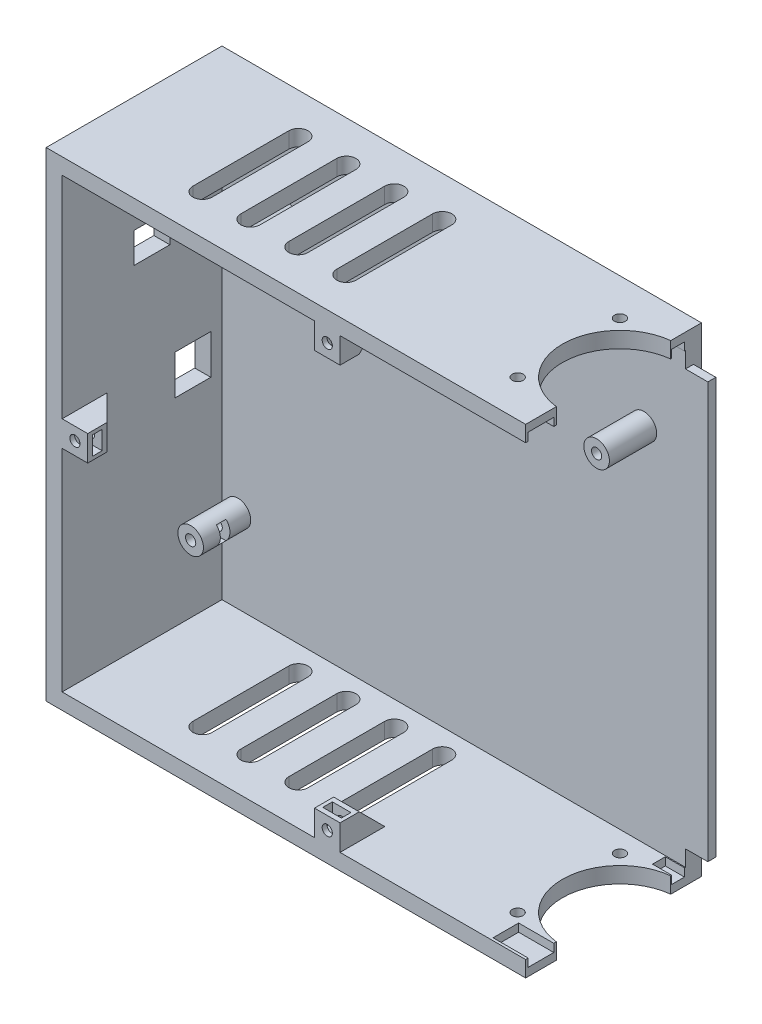
SolidWorks part; units mm, degrees
material "PLA"
ref_plane "Alzado" through (0, 0, 0) normal (0, 0, 1) x (1, 0, 0)
ref_plane "Planta" through (0, 0, 0) normal (0, 1, 0) x (1, 0, 0)
ref_plane "Vista lateral" through (0, 0, 0) normal (1, 0, 0) x (0, 0, -1)
sketch "Croquis1" plane through (0, 0, 0) normal (0, 0, 1) x (1, 0, 0)
  line L0 (-327.9437, 75) -> (-327.9437, -75)
  line L1 (-327.9437, 75) -> (-27.9437, 75)
  line L2 (-27.9437, 75) -> (-24, 71.0563)
  line L3 (-327.9437, -75) -> (-27.9437, -75)
  line L4 (-27.9437, -75) -> (-24, -71.0563)
  circle A0 centre (0, 0) radius 75 construction
  arc A1 (-24, 71.0563) -> (-24, -71.0563) centre (0, 0) ccw
  point P6 (-327.9437, 0)
  point P11 (-75, 0)
  dimension "D1" = 150
  dimension "D2" = 150
  dimension "D3" = 300
  dimension "D4" = 135
  dimension "D5" = 24
extrude "Saliente-Extruir1" add sketch "Croquis1" along normal blind 55
sketch "Croquis2" plane through (0, 0, 55) normal (0, 0, 1) x (1, 0, 0)
  line L2 (-27.9437, 70) -> (-327.9437, 70)
  line L3 (-38.7298, 70) -> (-322.9437, 70)
  line L5 (-322.9437, 75) -> (-322.9437, -75)
  line L6 (-322.9437, 70) -> (-322.9437, -70)
  line L8 (-327.9437, -70) -> (-27.9437, -70)
  line L9 (-322.9437, -70) -> (-38.7298, -70)
  arc A2 (-25.6, 75.7934) -> (-25.6, -75.7934) centre (0, 0) ccw
  arc A3 (-38.7298, 70) -> (-38.7298, -70) centre (0, 0) ccw
  dimension "D1" = 5
  dimension "D2" = 5
  dimension "D3" = 5
  dimension "D4" = 5
extrude "Cortar-Extruir1" cut sketch "Croquis2" against normal blind 50
sketch "Croquis3" plane through (0, 0, 0) normal (1, 0, 0) x (0, 0, -1)
  line L0 (-15, 7.5) -> (-15, -7.5) construction
  line L1 (-5, 7.5) -> (-5, -7.5)
  line L2 (-25, 7.5) -> (-25, -7.5)
  line L3 (-5, 70) -> (-5, -70) construction
  arc A0 (-5, 7.5) -> (-25, 7.5) centre (-15, 7.5) ccw
  arc A1 (-25, -7.5) -> (-5, -7.5) centre (-15, -7.5) ccw
  point P2 (-15, 0)
  dimension "D2" = 10
  dimension "D1" = 15
extrude "Cortar-Extruir2" cut sketch "Croquis3" against normal blind 82
sketch "Croquis4" plane through (0, 0, 0) normal (1, 0, 0) x (0, 0, -1)
  line L0 (-15, 30) -> (-15, -30) construction
  line L1 (-15, 30) -> (-45, 30) construction
  line L2 (-45, 30) -> (-45, -30) construction
  line L3 (-15, -30) -> (-45, -30) construction
  line L4 (-15, 30) -> (-45, -30) construction
  line L5 (-45, 30) -> (-15, -30) construction
  circle A0 centre (-45, -30) radius 2.6
  circle A1 centre (-15, -30) radius 2.6
  circle A2 centre (-15, 30) radius 2.6
  circle A3 centre (-45, 30) radius 2.6
  point P0 (-30, 0)
  dimension "D3" = 5.2
  dimension "D1" = 60
  dimension "D2" = 30
  dimension "D4" = 30
extrude "Cortar-Extruir3" cut sketch "Croquis4" against normal blind 82
ref_plane "Plano1" through (-80, 0, 0) normal (-1, 0, 0) x (0, 0, 1)
sketch "Croquis5" plane through (-80, 0, 0) normal (-1, 0, 0) x (0, 0, 1)
  circle A0 centre (45, -30) radius 2.6 construction
  circle A1 centre (15, -30) radius 2.6 construction
  circle A2 centre (45, 30) radius 2.6 construction
  circle A3 centre (15, 30) radius 2.6 construction
  circle A4 centre (45, -30) radius 2.6
  circle A5 centre (15, -30) radius 2.6
  circle A6 centre (45, 30) radius 2.6
  circle A7 centre (15, 30) radius 2.6
  circle A8 centre (45, 30) radius 5
  circle A9 centre (15, 30) radius 5
  circle A10 centre (45, -30) radius 5
  circle A11 centre (15, -30) radius 5
  dimension "D1" = 10
extrude "Saliente-Extruir2" add sketch "Croquis5" against normal up to surface (5.838 mm away) up to face at (-73.907, -30.6228, 47.5243)
sketch "Croquis6" plane through (0, 0, 5) normal (0, 0, 1) x (1, 0, 0)
  line L0 (-322.9437, 70) -> (-322.9437, -70) construction
  line L1 (-97.9437, -48) -> (-322.9437, -48) construction
  line L2 (-97.9437, -48) -> (-97.9437, 48) construction
  line L3 (-97.9437, 48) -> (-322.9437, 48) construction
  line L4 (-322.9437, -48) -> (-322.9437, 48) construction
  line L5 (-97.9437, -48) -> (-322.9437, 48) construction
  line L6 (-97.9437, 48) -> (-322.9437, -48) construction
  circle A0 centre (-302.9437, 44) radius 1.6
  circle A1 centre (-317.9437, -44) radius 1.6
  circle A2 centre (-190.9437, 43) radius 1.6
  circle A3 centre (-102.9437, 43) radius 1.6
  circle A4 centre (-102.9437, -43) radius 1.6
  point P0 (-210.4437, 0)
  dimension "D3" = 3.2
  dimension "D1" = 225
  dimension "D2" = 96
  dimension "D4" = 4
  dimension "D5" = 20
  dimension "D6" = 93
  dimension "D7" = 5
  dimension "D8" = 5
  dimension "D9" = 5
  dimension "D10" = 5
  dimension "D11" = 5
  dimension "D12" = 4
  dimension "D13" = 5
extrude "Cortar-Extruir4" cut sketch "Croquis6" against normal blind 82
sketch "Croquis7" plane through (-327.9437, 0, 0) normal (-1, 0, 0) x (0, 0, 1)
  line L0 (55, 75) -> (55, -75) construction
  line L1 (21.3, 43.8) -> (32.5, 43.8)
  line L2 (21.3, 43.8) -> (21.3, 34.3)
  line L3 (21.3, 34.3) -> (32.5, 34.3)
  line L4 (32.5, 43.8) -> (32.5, 34.3)
  line L5 (21.3, 43.8) -> (32.5, 34.3) construction
  line L6 (21.3, 34.3) -> (32.5, 43.8) construction
  line L7 (55, 75) -> (0, 75) construction
  point P0 (26.9, 39.05)
  dimension "D1" = 22.5
  dimension "D2" = 31.2
  dimension "D3" = 11.2
  dimension "D4" = 9.5
extrude "Cortar-Extruir5" cut sketch "Croquis7" against normal blind 13
sketch "Croquis8" plane through (-327.9437, 0, 0) normal (-1, 0, 0) x (0, 0, 1)
  line L0 (0, 75) -> (0, -75) construction
  line L1 (19.7, -8) -> (8.5, -8)
  line L2 (19.7, -8) -> (19.7, 4.4)
  line L3 (19.7, 4.4) -> (8.5, 4.4)
  line L4 (8.5, -8) -> (8.5, 4.4)
  line L5 (19.7, -8) -> (8.5, 4.4) construction
  line L6 (19.7, 4.4) -> (8.5, -8) construction
  line L7 (55, -75) -> (0, -75) construction
  point P0 (14.1, -1.8)
  point P9 (14.1, -8)
  dimension "D1" = 8.5
  dimension "D2" = 67
  dimension "D3" = 11.2
  dimension "D4" = 12.4
extrude "Cortar-Extruir6" cut sketch "Croquis8" against normal blind 13
sketch "Croquis9" plane through (0, 0, 5) normal (0, 0, 1) x (1, 0, 0)
  circle A0 centre (-302.9437, 44) radius 4
  circle A1 centre (-317.9437, -44) radius 4
  circle A2 centre (-190.9437, 43) radius 4
  circle A3 centre (-102.9437, 43) radius 4
  circle A4 centre (-102.9437, -43) radius 4
  circle A5 centre (-190.9437, 43) radius 1.6 construction
  circle A6 centre (-317.9437, -44) radius 1.6 construction
  circle A7 centre (-102.9437, 43) radius 1.6 construction
  circle A8 centre (-102.9437, -43) radius 1.6 construction
  circle A9 centre (-102.9437, -43) radius 1.6
  circle A10 centre (-102.9437, 43) radius 1.6
  circle A11 centre (-317.9437, -44) radius 1.6
  circle A12 centre (-190.9437, 43) radius 1.6
  circle A13 centre (-302.9437, 44) radius 1.6 construction
  circle A14 centre (-302.9437, 44) radius 1.6
  dimension "D1" = 8
extrude "Saliente-Extruir3" add sketch "Croquis9" along normal blind 14.8
sketch "Croquis10" plane through (0, -75, 0) normal (0, -1, 0) x (1, 0, 0)
  line L0 (-159.9437, 11.5) -> (-191.9437, 11.5) construction
  line L1 (-159.9437, 11.5) -> (-159.9437, 43.5) construction
  line L2 (-159.9437, 43.5) -> (-191.9437, 43.5) construction
  line L3 (-191.9437, 11.5) -> (-191.9437, 43.5) construction
  line L4 (-159.9437, 11.5) -> (-191.9437, 43.5) construction
  line L5 (-159.9437, 43.5) -> (-191.9437, 11.5) construction
  line L6 (-107.9437, 11.5) -> (-139.9437, 11.5) construction
  line L7 (-107.9437, 11.5) -> (-107.9437, 43.5) construction
  line L8 (-107.9437, 43.5) -> (-139.9437, 43.5) construction
  line L9 (-139.9437, 11.5) -> (-139.9437, 43.5) construction
  line L10 (-107.9437, 11.5) -> (-139.9437, 43.5) construction
  line L11 (-107.9437, 43.5) -> (-139.9437, 11.5) construction
  line L12 (-327.9437, 55) -> (-327.9437, 0) construction
  line L13 (-27.9437, 55) -> (-27.9437, 0) construction
  circle A0 centre (-191.9437, 43.5) radius 1.7
  circle A1 centre (-159.9437, 43.5) radius 1.7
  circle A2 centre (-191.9437, 11.5) radius 1.7
  circle A3 centre (-159.9437, 11.5) radius 1.7
  circle A4 centre (-139.9437, 43.5) radius 1.7
  circle A5 centre (-107.9437, 43.5) radius 1.7
  circle A6 centre (-139.9437, 11.5) radius 1.7
  circle A7 centre (-107.9437, 11.5) radius 1.7
  circle A12 centre (-175.9437, 27.5) radius 18
  circle A13 centre (-123.9437, 27.5) radius 18
  point P4 (-175.9437, 27.5)
  point P13 (-123.9437, 27.5)
  point P20 (-327.9437, 27.5)
  dimension "D3" = 3.4
  dimension "D6" = 3.4
  dimension "D9" = 36
  dimension "D1" = 32
  dimension "D2" = 32
  dimension "D4" = 32
  dimension "D5" = 32
  dimension "D7" = 20
  dimension "D8" = 80
extrude "Cortar-Extruir7" cut sketch "Croquis10" against normal blind 14.8
mirror "Simetría1" about plane through (0, 0, 0) normal (0, 1, 0) of "Cortar-Extruir7"
ref_plane "Plano2" through (0, 0, 13) normal (0, 0, 1) x (1, 0, 0)
sketch "Croquis11" plane through (0, 0, 13) normal (0, 0, 1) x (1, 0, 0)
  line L0 (-301.2687, 46.9012) -> (-296.5962, 46.9012)
  line L1 (-299.5937, 44) -> (-301.2687, 46.9012) construction
  line L2 (-301.2687, 46.9012) -> (-304.6187, 46.9012)
  line L3 (-304.6187, 46.9012) -> (-306.2937, 44)
  line L4 (-306.2937, 44) -> (-304.6187, 41.0988)
  line L5 (-304.6187, 41.0988) -> (-301.2687, 41.0988)
  line L6 (-301.2687, 41.0988) -> (-299.5937, 44) construction
  line L7 (-314.5937, -44) -> (-316.2687, -41.0988) construction
  line L8 (-316.2687, -41.0988) -> (-319.6187, -41.0988)
  line L9 (-319.6187, -41.0988) -> (-321.2937, -44)
  line L10 (-321.2937, -44) -> (-319.6187, -46.9012)
  line L11 (-319.6187, -46.9012) -> (-316.2687, -46.9012)
  line L12 (-316.2687, -46.9012) -> (-314.5937, -44) construction
  line L13 (-187.5937, 43) -> (-189.2687, 45.9012)
  line L14 (-189.2687, 45.9012) -> (-192.6187, 45.9012)
  line L15 (-192.6187, 45.9012) -> (-194.2937, 43) construction
  line L16 (-194.2937, 43) -> (-192.6187, 40.0988) construction
  line L17 (-192.6187, 40.0988) -> (-189.2687, 40.0988)
  line L18 (-189.2687, 40.0988) -> (-187.5937, 43)
  line L19 (-99.5937, 43) -> (-101.2687, 45.9012)
  line L20 (-101.2687, 45.9012) -> (-104.6187, 45.9012)
  line L21 (-104.6187, 45.9012) -> (-106.2937, 43) construction
  line L22 (-106.2937, 43) -> (-104.6187, 40.0988) construction
  line L23 (-104.6187, 40.0988) -> (-101.2687, 40.0988)
  line L24 (-101.2687, 40.0988) -> (-99.5937, 43)
  line L25 (-99.5937, -43) -> (-101.2687, -40.0988)
  line L26 (-101.2687, -40.0988) -> (-104.6187, -40.0988)
  line L27 (-104.6187, -40.0988) -> (-106.2937, -43) construction
  line L28 (-106.2937, -43) -> (-104.6187, -45.9012) construction
  line L29 (-104.6187, -45.9012) -> (-101.2687, -45.9012)
  line L30 (-101.2687, -45.9012) -> (-99.5937, -43)
  line L31 (-296.5962, 46.9012) -> (-296.5962, 41.0988)
  line L32 (-296.5962, 41.0988) -> (-301.2687, 41.0988)
  line L33 (-192.6187, 45.9012) -> (-196.6834, 45.9012)
  line L34 (-196.6834, 45.9012) -> (-196.6834, 40.0988)
  line L35 (-196.6834, 40.0988) -> (-192.6187, 40.0988)
  line L36 (-104.6187, 45.9012) -> (-110.7706, 45.9012)
  line L37 (-110.7706, 45.9012) -> (-110.7706, 40.0988)
  line L38 (-110.7706, 40.0988) -> (-104.6187, 40.0988)
  line L39 (-104.6187, -40.0988) -> (-109.0472, -40.0988)
  line L40 (-109.0472, -40.0988) -> (-109.1678, -45.9012)
  line L41 (-109.1678, -45.9012) -> (-104.6187, -45.9012)
  line L42 (-316.2687, -46.9012) -> (-310.7216, -46.9012)
  line L43 (-310.7216, -46.9012) -> (-310.7216, -41.0988)
  line L44 (-310.7216, -41.0988) -> (-316.2687, -41.0988)
  line L45 (-38.7298, 70) -> (-322.9437, 70) construction
  line L46 (-322.9437, -70) -> (-38.7298, -70) construction
  circle A0 centre (-302.9437, 44) radius 3.35 construction
  circle A1 centre (-317.9437, -44) radius 3.35 construction
  circle A2 centre (-190.9437, 43) radius 3.35 construction
  circle A3 centre (-102.9437, 43) radius 3.35 construction
  circle A4 centre (-102.9437, -43) radius 3.35 construction
  dimension "D1" = 6.7
extrude "Cortar-Extruir8" cut sketch "Croquis11" against normal blind 1.5 and the other way blind 1.5
sketch "Croquis12" plane through (0, 0, 0) normal (0, 1, 0) x (1, 0, 0)
  line L0 (-322.9437, -41) -> (-322.9437, -55)
  line L1 (-322.9437, -55) -> (-314.9437, -55)
  line L6 (-27.9437, -55) -> (-327.9437, -55) construction
  line L7 (-322.9437, -19.7) -> (-322.9437, -8.5) construction
  line L8 (-314.9437, -55) -> (-314.9437, -49)
  line L9 (-314.9437, -49) -> (-322.9437, -41)
  dimension "D1" = 8
  dimension "D2" = 45
  dimension "D3" = 6
extrude "Saliente-Extruir4" add sketch "Croquis12" along normal blind 4 and the other way blind 4
sketch "Croquis14" plane through (-80, 0, 0) normal (-1, 0, 0) x (0, 0, 1)
  line L0 (55, 70) -> (55, 62)
  line L1 (55, -70) -> (55, 70) construction
  line L3 (5, 70) -> (55, 70) construction
  line L4 (41, 70) -> (55, 70)
  line L5 (55, -70) -> (55, -62)
  line L7 (5, -70) -> (55, -70) construction
  line L8 (41, -70) -> (55, -70)
  line L9 (55, 62) -> (49, 62)
  line L10 (49, 62) -> (41, 70)
  line L11 (41, -70) -> (49, -62)
  line L12 (49, -62) -> (55, -62)
  dimension "D2" = 8
  dimension "D3" = 45
  dimension "D4" = 8
  dimension "D5" = 6
extrude "Saliente-Extruir5" add sketch "Croquis14" along normal blind 4 and the other way blind 4
sketch "Croquis13" plane through (0, 0, 55) normal (0, 0, 1) x (1, 0, 0)
  line L0 (-322.9437, 4) -> (-314.9437, -4) construction
  line L1 (-314.9437, 4) -> (-322.9437, -4) construction
  line L2 (-84, 70) -> (-76, 62) construction
  line L4 (-76, 70) -> (-84, 62) construction
  line L6 (-84, -62) -> (-76, -70) construction
  line L7 (-84, -70) -> (-76, -62) construction
  line L8 (-76, -70) -> (-76, -62) construction
  line L9 (-84, -70) -> (-84, -62) construction
  circle A0 centre (-318.9437, 0) radius 1.6
  circle A2 centre (-80, -66) radius 1.6
  circle A3 centre (-80, 66) radius 1.6
  dimension "D1" = 3.2
extrude "Cortar-Extruir9" cut sketch "Croquis13" against normal blind 14
ref_plane "Plano3" through (-160, 0, 0) normal (-1, 0, 0) x (0, 0, 1)
ref_plane "Plano4" through (0, 0, 52) normal (0, 0, 1) x (1, 0, 0)
mirror "Simetría2" about plane through (-160, 0, 0) normal (-1, 0, 0) of "Cortar-Extruir9", "Saliente-Extruir5"
sketch "Croquis17" plane through (0, 0, 52) normal (0, 0, 1) x (1, 0, 0)
  line L0 (-322.9437, 70) -> (-322.9437, 4) construction
  line L1 (-315.5937, 0) -> (-317.2687, 2.9012) construction
  line L2 (-317.2687, 2.9012) -> (-320.6187, 2.9012)
  line L3 (-320.6187, 2.9012) -> (-322.2937, 0)
  line L4 (-322.2937, 0) -> (-320.6187, -2.9012)
  line L5 (-320.6187, -2.9012) -> (-317.2687, -2.9012)
  line L6 (-317.2687, -2.9012) -> (-315.5937, 0) construction
  line L7 (-240, -62.65) -> (-242.9012, -64.325) construction
  line L8 (-242.9012, -64.325) -> (-242.9012, -67.675)
  line L9 (-242.9012, -67.675) -> (-240, -69.35)
  line L10 (-240, -69.35) -> (-237.0988, -67.675)
  line L11 (-237.0988, -67.675) -> (-237.0988, -64.325)
  line L12 (-237.0988, -64.325) -> (-240, -62.65) construction
  line L13 (-80, -62.65) -> (-82.9012, -64.325) construction
  line L14 (-82.9012, -64.325) -> (-82.9012, -67.675)
  line L15 (-82.9012, -67.675) -> (-80, -69.35)
  line L16 (-80, -69.35) -> (-77.0988, -67.675)
  line L17 (-77.0988, -67.675) -> (-77.0988, -64.325)
  line L18 (-77.0988, -64.325) -> (-80, -62.65) construction
  line L19 (-80, 62.65) -> (-77.0988, 64.325) construction
  line L20 (-77.0988, 64.325) -> (-77.0988, 67.675)
  line L21 (-77.0988, 67.675) -> (-80, 69.35)
  line L22 (-80, 69.35) -> (-82.9012, 67.675)
  line L23 (-82.9012, 67.675) -> (-82.9012, 64.325)
  line L24 (-82.9012, 64.325) -> (-80, 62.65) construction
  line L25 (-240, 62.65) -> (-237.0988, 64.325) construction
  line L26 (-237.0988, 64.325) -> (-237.0988, 67.675)
  line L27 (-237.0988, 67.675) -> (-240, 69.35)
  line L28 (-240, 69.35) -> (-242.9012, 67.675)
  line L29 (-242.9012, 67.675) -> (-242.9012, 64.325)
  line L30 (-242.9012, 64.325) -> (-240, 62.65) construction
  line L31 (-322.9437, -70) -> (-244, -70) construction
  line L32 (-317.2687, 2.9012) -> (-310.6187, 2.9012)
  line L33 (-310.6187, 2.9012) -> (-310.6187, -2.9012)
  line L34 (-310.6187, -2.9012) -> (-317.2687, -2.9012)
  line L35 (-242.9012, 64.325) -> (-242.9012, 57.675)
  line L36 (-242.9012, 57.675) -> (-237.0988, 57.675)
  line L37 (-237.0988, 57.675) -> (-237.0988, 64.325)
  line L38 (-82.9012, 64.325) -> (-82.9012, 57.675)
  line L39 (-82.9012, 57.675) -> (-76.8873, 57.675)
  line L40 (-76.8873, 57.675) -> (-77.0988, 64.325)
  line L41 (-82.9012, -64.325) -> (-82.9012, -57.675)
  line L42 (-82.9012, -57.675) -> (-77.0988, -57.675)
  line L43 (-77.0988, -57.675) -> (-77.0988, -64.325)
  line L44 (-242.9012, -64.325) -> (-242.9012, -57.675)
  line L45 (-242.9012, -57.675) -> (-237.0988, -57.675)
  line L46 (-237.0988, -57.675) -> (-237.0988, -64.325)
  circle A0 centre (-318.9437, 0) radius 3.35 construction
  circle A1 centre (-240, -66) radius 3.35 construction
  circle A2 centre (-80, -66) radius 3.35 construction
  circle A3 centre (-80, 66) radius 3.35 construction
  circle A4 centre (-240, 66) radius 3.35 construction
  dimension "D1" = 6.7
  dimension "D2" = 10
extrude "Cortar-Extruir10" cut sketch "Croquis17" against normal blind 1.5 and the other way blind 1.5
sketch "Croquis18" plane through (0, 0, 0) normal (0, 0, 1) x (1, 0, 0)
  line L1 (-17.9437, -110) -> (-177.9437, -110)
  line L2 (-17.9437, -110) -> (-17.9437, 110)
  line L3 (-17.9437, 110) -> (-177.9437, 110)
  line L4 (-177.9437, -110) -> (-177.9437, 110)
  line L5 (-17.9437, -110) -> (-177.9437, 110) construction
  line L6 (-17.9437, 110) -> (-177.9437, -110) construction
  line L9 (-327.9437, 75) -> (-327.9437, -75) construction
  point P0 (-97.9437, 0)
  dimension "D1" = 150
  dimension "D2" = 220
extrude "Cortar-Extruir11" cut sketch "Croquis18" along normal blind 89.5 contours L3 L4 L1 L2
sketch "Croquis20" plane through (0, -70, 0) normal (0, 1, 0) x (1, 0, 0)
  line L0 (-177.9437, -9.6115) -> (-177.9437, -5) construction
  line L1 (-183.9437, -5.3057) -> (-171.9437, -5.3057)
  line L2 (-183.9437, -5.3057) -> (-183.9437, -9.3057)
  line L3 (-183.9437, -9.3057) -> (-171.9437, -9.3057)
  line L4 (-171.9437, -5.3057) -> (-171.9437, -9.3057)
  line L5 (-183.9437, -5.3057) -> (-171.9437, -9.3057) construction
  line L6 (-183.9437, -9.3057) -> (-171.9437, -5.3057) construction
  line L7 (-177.9437, -55) -> (-177.9437, -45.3885) construction
  line L8 (-188.9437, -46.1943) -> (-166.9437, -46.1943)
  line L9 (-188.9437, -46.1943) -> (-188.9437, -54.1943)
  line L10 (-188.9437, -54.1943) -> (-166.9437, -54.1943)
  line L11 (-166.9437, -46.1943) -> (-166.9437, -54.1943)
  line L12 (-188.9437, -46.1943) -> (-166.9437, -54.1943) construction
  line L13 (-188.9437, -54.1943) -> (-166.9437, -46.1943) construction
  point P0 (-177.9437, -7.3057)
  point P7 (-177.9437, -50.1943)
  dimension "D1" = 12
  dimension "D2" = 22
  dimension "D3" = 8
  dimension "D4" = 4
extrude "Cortar-Extruir12" cut sketch "Croquis20" against normal blind 2.5
mirror "Simetría3" about plane through (0, 0, 0) normal (0, 1, 0) of "Cortar-Extruir12"
sketch "Croquis21" plane through (0, 0, 5) normal (0, 0, 1) x (1, 0, 0)
  line L0 (-177.9437, 70) -> (-177.9437, -70) construction
  line L1 (-184.9437, -65) -> (-170.9437, -65)
  line L2 (-184.9437, -65) -> (-184.9437, 65)
  line L3 (-184.9437, 65) -> (-170.9437, 65)
  line L4 (-170.9437, -65) -> (-170.9437, 65)
  line L5 (-184.9437, -65) -> (-170.9437, 65) construction
  line L6 (-184.9437, 65) -> (-170.9437, -65) construction
  point P0 (-177.9437, 0)
  dimension "D1" = 14
  dimension "D2" = 130
extrude "Saliente-Extruir6" add sketch "Croquis21" against normal blind 2.5
sketch "Croquis23" plane through (0, -75, 0) normal (0, -1, 0) x (1, 0, 0)
  line L0 (-276.5321, 42.5) -> (-276.5321, 12.5) construction
  line L1 (-273.5321, 42.5) -> (-273.5321, 12.5)
  line L2 (-279.5321, 42.5) -> (-279.5321, 12.5)
  line L3 (-261.5321, 42.5) -> (-261.5321, 12.5) construction
  line L4 (-258.5321, 42.5) -> (-258.5321, 12.5)
  line L5 (-264.5321, 42.5) -> (-264.5321, 12.5)
  line L6 (-246.5321, 42.5) -> (-246.5321, 12.5) construction
  line L7 (-243.5321, 42.5) -> (-243.5321, 12.5)
  line L8 (-249.5321, 42.5) -> (-249.5321, 12.5)
  line L9 (-291.5321, 42.5) -> (-291.5321, 12.5) construction
  line L10 (-288.5321, 42.5) -> (-288.5321, 12.5)
  line L11 (-294.5321, 42.5) -> (-294.5321, 12.5)
  line L12 (-317.9437, 55) -> (-317.9437, 0) construction
  line L13 (-327.9437, 55) -> (-177.9437, 55) construction
  line L14 (-327.9437, 0) -> (-177.9437, 0) construction
  line L15 (-327.9437, 55) -> (-327.9437, 0) construction
  arc A0 (-273.5321, 42.5) -> (-279.5321, 42.5) centre (-276.5321, 42.5) ccw
  arc A1 (-279.5321, 12.5) -> (-273.5321, 12.5) centre (-276.5321, 12.5) ccw
  arc A2 (-258.5321, 42.5) -> (-264.5321, 42.5) centre (-261.5321, 42.5) ccw
  arc A3 (-264.5321, 12.5) -> (-258.5321, 12.5) centre (-261.5321, 12.5) ccw
  arc A4 (-243.5321, 42.5) -> (-249.5321, 42.5) centre (-246.5321, 42.5) ccw
  arc A5 (-249.5321, 12.5) -> (-243.5321, 12.5) centre (-246.5321, 12.5) ccw
  arc A6 (-288.5321, 42.5) -> (-294.5321, 42.5) centre (-291.5321, 42.5) ccw
  arc A7 (-294.5321, 12.5) -> (-288.5321, 12.5) centre (-291.5321, 12.5) ccw
  point P2 (-276.5321, 27.5)
  point P7 (-261.5321, 27.5)
  point P14 (-246.5321, 27.5)
  point P21 (-291.5321, 27.5)
  point P36 (-317.9437, 27.5)
  dimension "D1" = 10
  dimension "D2" = 15
  dimension "D3" = 15
  dimension "D4" = 15
  dimension "D5" = 30
  dimension "D6" = 30
  dimension "D7" = 6
extrude "Cortar-Extruir13" cut sketch "Croquis23" against normal blind 300
sketch "Croquis25" plane through (-327.9437, 0, 0) normal (-1, 0, 0) x (0, 0, 1)
  text T0 "\r\n\r\n\r\n\r\n\r\n\r\n\r\n\r\nProyecto Graduación  \r\nSemestre 2 2022            \r\nAlejandro Gómez         " font "Century Gothic" height 2.5
extrude "Cortar-Extruir14" cut sketch "Croquis25" against normal blind 1
